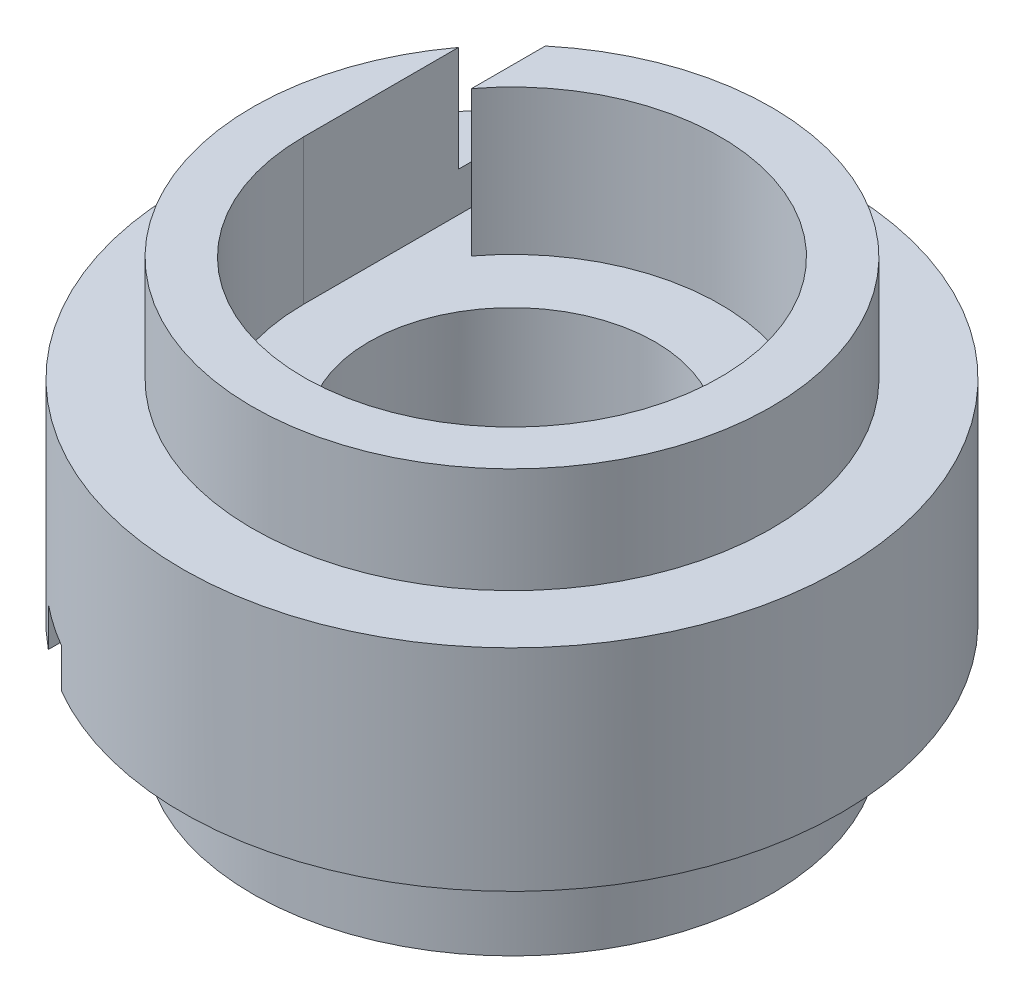
SolidWorks part; units mm, degrees
ref_plane "Front Plane" through (0, 0, 0) normal (0, 0, 1) x (1, 0, 0)
ref_plane "Top Plane" through (0, 0, 0) normal (0, 1, 0) x (1, 0, 0)
ref_plane "Right Plane" through (0, 0, 0) normal (1, 0, 0) x (0, 0, -1)
sketch "Sketch1" plane through (0, 0, 0) normal (0, 1, 0) x (1, 0, 0)
  circle A0 centre (0, 0) radius 31.75
  circle A1 centre (0, 0) radius 13.7886
  dimension "D1" = 63.5
extrude "Boss-Extrude1" add sketch "Sketch1" along normal mid plane 40.64
sketch "Sketch2" plane through (0, 20.32, 0) normal (0, 1, 0) x (1, 0, 0)
  line L0 (-20.066, 0) -> (-20.066, 24.6052)
  line L1 (-16.002, 12.107) -> (-16.002, 27.4226)
  arc A0 (-20.066, 0) -> (-16.002, 12.107) centre (0, 0) ccw
  circle A1 centre (0, 0) radius 31.75 construction
  arc A2 (-16.002, 27.4226) -> (-20.066, 24.6052) centre (0, 0) ccw
  dimension "D1" = 4.064
extrude "Cut-Extrude1" cut sketch "Sketch2" against normal blind 13.97
sketch "Sketch13" plane through (0, 20.32, 0) normal (0, 1, 0) x (1, 0, 0)
  circle A1 centre (0, 0) radius 25
  circle A2 centre (0, 0) radius 31.75
  arc A3 (-20.066, 24.6052) -> (-16.002, 27.4226) centre (0, 0) ccw construction
extrude "Cut-Extrude2" cut sketch "Sketch13" against normal blind 10.16
sketch "Sketch5" plane through (0, 0, 0) normal (0, 1, 0) x (1, 0, 0)
  line L0 (0, -39.3443) -> (0, 40.2571) construction
  line L1 (0, -22.352) -> (0, 22.352) construction
ref_axis "Axis1" through (34.925, 0, 0) along (-1, 0, 0)
sketch "Sketch9" plane through (0, 0, 0) normal (0, 0, 1) x (1, 0, 0)
  line L0 (0, -22.352) -> (0, 22.352) construction
  line L1 (-20.066, 3.81) -> (-14.478, 3.81)
  line L2 (-20.066, 3.81) -> (-20.066, 0)
  line L3 (-20.066, 0) -> (-14.478, 0)
  line L4 (-14.478, 3.81) -> (-14.478, 0)
  point P5 (-14.478, 1.905)
  dimension "D1" = 3.81
  dimension "D2" = 14.478
sketch "Sketch12" plane through (0, 6.35, 0) normal (0, 1, 0) x (1, 0, 0)
  circle A0 centre (0, 0) radius 13.7886
  circle A1 centre (0, 0) radius 13.7886 construction
curve "Helix/Spiral2" pitch 3.302 height 2.9619 turns 0.897
pattern_circular "CirPattern1" count 2 every 180 about axis through (34.925, 0, 0) along (-1, 0, 0) of "Cut-Extrude2", "Cut-Extrude1"
